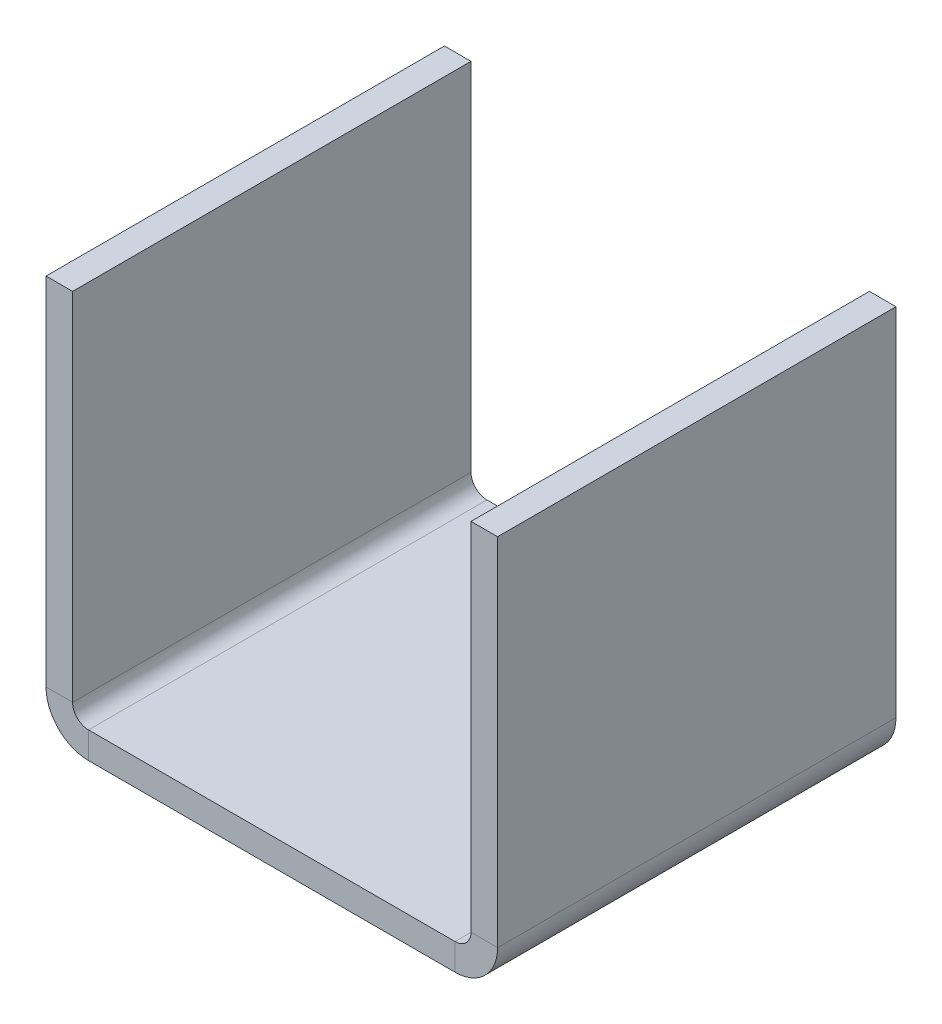
SolidWorks part; units mm, degrees
note: The reader was unsure of these and kept them because the rebuilt part matched: flange length of "Edge-Flange1".
ref_plane "Front Plane" through (0, 0, 0) normal (0, 0, 1) x (1, 0, 0)
ref_plane "Top Plane" through (0, 0, 0) normal (0, 1, 0) x (1, 0, 0)
ref_plane "Right Plane" through (0, 0, 0) normal (1, 0, 0) x (0, 0, -1)
sketch "Sketch1" plane through (0, 0, 0) normal (0, 1, 0) x (1, 0, 0)
  line L1 (-13.8, 15) -> (13.8, 15)
  line L2 (-13.8, 15) -> (-13.8, -15)
  line L3 (-13.8, -15) -> (13.8, -15)
  line L4 (13.8, 15) -> (13.8, -15)
  line L5 (-13.8, 15) -> (13.8, -15) construction
  line L6 (-13.8, -15) -> (13.8, 15) construction
  point P0 (0, 0)
  dimension "D1" = 27.6
  dimension "D2" = 30
base flange "Base-Flange1" sketch "Sketch1" thickness 2 reverse thickness direction no parameters "D1"=0.7366
edge flange "Edge-Flange1" sketch "Sketch10" flange profiles "Sketch10", "Sketch11" flange angle 90 flange length 30 flange position bend outside bend radius 1.2 thickness 2 relief rectangular parameters "D6"=10, "D8"=1
sketch "Sketch10" plane through (13.8, 0, 0) normal (1, 0, 0) x (0, 0, -1)
  line L2 (-15, 0) -> (-15, 28)
  line L3 (-15, 28) -> (15, 28)
  line L4 (15, 28) -> (15, 0)
  line L7 (-15, 0) -> (15, 0) construction
  line L8 (-15, 0) -> (15, 0)
sketch "Sketch11" plane through (-13.8, 0, 0) normal (-1, 0, 0) x (0, 0, 1)
  line L0 (-15, 0) -> (15, 0) construction
  line L1 (-15, 0) -> (15, 0)
  line L2 (-15, 0) -> (-15, 28)
  line L3 (-15, 28) -> (15, 28)
  line L4 (15, 28) -> (15, 0)
bend "EdgeBend1" bend radius 1.2 bend angle 90 parameters "D5"=1
bend "EdgeBend2" bend radius 1.2 bend angle 90 parameters "D5"=2
edge flange "Edge-Flange2" [suppressed] sketch "Sketch14" flange profiles "Sketch14", "Sketch19" flange angle 90 flange position bend outside bend radius 1.2 thickness 2
sketch "Sketch14" plane through (-15, 28, 0) normal (0, 1, 0) x (0, 0, 1)
  line L0 (15, 0) -> (-15, 0) construction
  line L1 (15, 0) -> (-15, 0)
  line L2 (-15, 0) -> (-15, 14.5)
  line L3 (-15, 14.5) -> (15, 14.5)
  line L4 (15, 14.5) -> (15, 0)
sketch "Sketch19" plane through (15, 28, 0) normal (0, 1, 0) x (0, 0, -1)
  line L0 (15, 0) -> (-15, 0) construction
  line L1 (15, 0) -> (-15, 0)
  line L2 (-15, 0) -> (-15, 14.5)
  line L3 (-15, 14.5) -> (15, 14.5)
  line L4 (15, 14.5) -> (15, 0)
bend "EdgeBend3" bend radius 1.2 bend angle 90 parameters "D5"=3
bend "EdgeBend5" bend radius 1.2 bend angle 90 parameters "D5"=5, "D6"=10, "D7"=16.5
sketch "Bend-Lines1" [suppressed] plane through (0, 0, 0) normal (0, 1, 0) x (1, 0, 0)
sketch "Bounding-Box1" [suppressed] plane through (0, 0, 0) normal (0, 1, 0) x (1, 0, 0)
sheet metal parameters "Sheet-Metal1" thickness 2 parameters "D1"=0.7366
flat pattern "Flat-Pattern1" [suppressed]
sketch "Bend-Lines2" plane through (0, 0, 0) normal (0, 1, 0) x (1, 0, 0)
sketch3d "Bounding-Box2" [suppressed]
  line L0 (-15, -15, 0) -> (15, -15, 0) construction
  line L1 (-15, 15, 0) -> (15, 15, 0) construction
  line L2 (-15, -15, 0) -> (-15, 15, 0) construction
  line L3 (15, -15, 0) -> (15, 15, 0) construction
sheet metal parameters "Sheet-Metal2" thickness 2 parameters "D1"=0.7366
flat pattern "Flat-Pattern1"
sketch "Bend-Lines2" plane through (0, 0, 0) normal (0, 1, 0) x (1, 0, 0)
  line L0 (-15.5279, 15) -> (-15.5279, -15) construction
  line L1 (15.5279, -15) -> (15.5279, 15) construction
  line L2 (-15.5279, 15) -> (-15.5279, -15) construction
  line L3 (15.5279, -15) -> (15.5279, 15) construction
sketch3d "Bounding-Box2" [suppressed]
  line L0 (44.0558, -15, 0) -> (-44.0558, -15, 0) construction
  line L1 (44.0558, 15, 0) -> (-44.0558, 15, 0) construction
  line L2 (44.0558, -15, 0) -> (44.0558, 15, 0) construction
  line L3 (-44.0558, -15, 0) -> (-44.0558, 15, 0) construction
bend of the flat pattern "Flatten-<EdgeBend1>1"
bend of the flat pattern "Flatten-<EdgeBend2>1"
sheet metal parameters "Sheet-Metal3" thickness 2 parameters "D1"=0.7366
flat pattern "Flat-Pattern1"
sketch "Bend-Lines2" plane through (0, 0, 0) normal (0, 1, 0) x (1, 0, 0)
  line L0 (-15.5279, 15) -> (-15.5279, -15) construction
  line L1 (15.5279, -15) -> (15.5279, 15) construction
  line L2 (-15.5279, 15) -> (-15.5279, -15) construction
  line L3 (15.5279, -15) -> (15.5279, 15) construction
  line L4 (-45.7836, 15) -> (-45.7836, -15) construction
  line L5 (-45.7836, 15) -> (-45.7836, -15) construction
  line L6 (45.7836, -15) -> (45.7836, 15) construction
  line L7 (45.7836, -15) -> (45.7836, 15) construction
sketch3d "Bounding-Box2" [suppressed]
  line L0 (60.8115, -15, 0) -> (-60.8115, -15, 0) construction
  line L1 (60.8115, 15, 0) -> (-60.8115, 15, 0) construction
  line L2 (60.8115, -15, 0) -> (60.8115, 15, 0) construction
  line L3 (-60.8115, -15, 0) -> (-60.8115, 15, 0) construction
bend of the flat pattern "Flatten-<EdgeBend1>1"
bend of the flat pattern "Flatten-<EdgeBend2>1"
bend of the flat pattern "Flatten-<EdgeBend3>1"
bend of the flat pattern "Flatten-<EdgeBend5>1"
